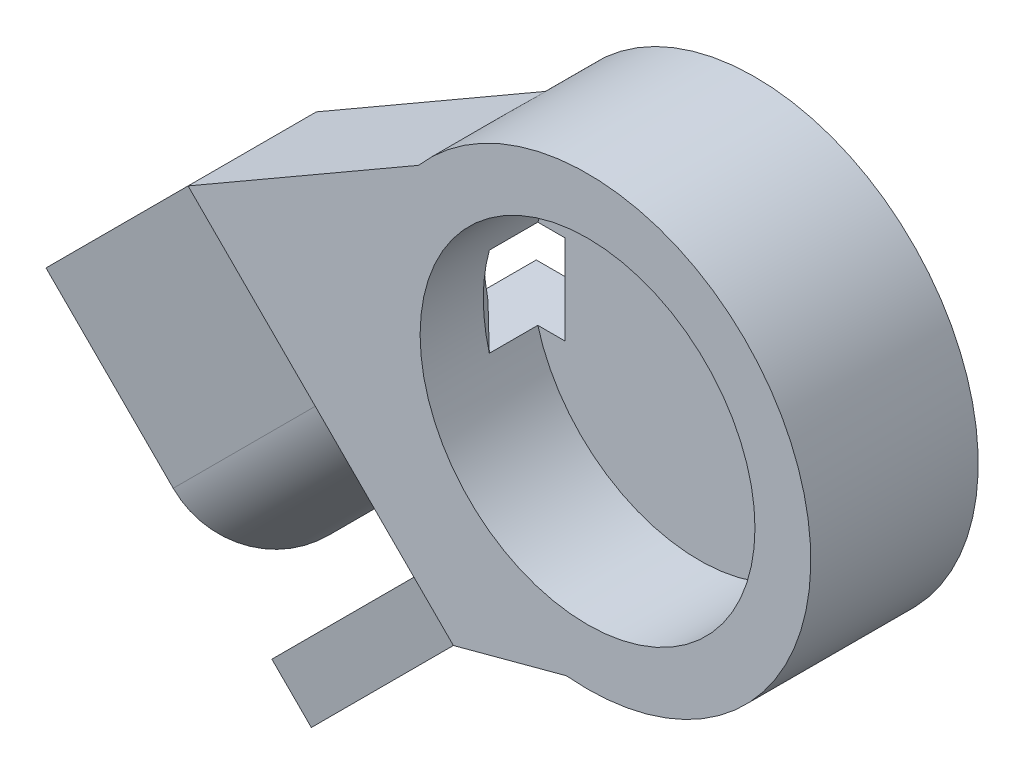
SolidWorks part; units mm, degrees
material "ABS"
ref_plane "Front Plane" through (0, 0, 0) normal (0, 0, 1) x (1, 0, 0)
ref_plane "Top Plane" through (0, 0, 0) normal (0, 1, 0) x (1, 0, 0)
ref_plane "Right Plane" through (0, 0, 0) normal (1, 0, 0) x (0, 0, -1)
ref_plane "Plane1" through (176.1577, 176.1577, 66.7527) normal (0.683, 0.683, 0.2588) x (0.7241, -0.6798, -0.1169)
sketch "Sketch2" plane through (176.1577, 176.1577, 66.7527) normal (0.683, 0.683, 0.2588) x (0.7241, -0.6798, -0.1169)
  line L0 (-5.3415, 21.7837) -> (-15.5015, 23.0219)
  line L1 (-2.3354, 33.3275) -> (-3.5736, 23.1675)
  line L2 (-15.5015, 23.0219) -> (-15.8856, 19.8702)
  line L3 (-2.3354, 33.3275) -> (0.8163, 32.9434)
  line L4 (-1.8445, 37.3551) -> (-3.5736, 23.1675) construction
  line L5 (-5.3415, 21.7837) -> (-19.5291, 23.5127) construction
  line L6 (1.7696, 14.5201) -> (4.8423, 39.7335)
  line L7 (4.8423, 39.7335) -> (4.8373, 39.7342)
  line L8 (1.3071, 36.971) -> (-0.4219, 22.7834)
  line L9 (-5.7256, 18.632) -> (-19.9132, 20.361)
  line L10 (-23.4433, 17.5979) -> (-23.4439, 17.5928)
  line L11 (-23.4439, 17.5928) -> (1.7696, 14.5201)
  line L12 (1.7696, 14.5201) -> (4.8423, 39.7335)
  line L13 (4.8423, 39.7335) -> (4.8373, 39.7342)
  line L14 (1.3071, 36.971) -> (-0.4219, 22.7834)
  line L15 (-5.7256, 18.632) -> (-19.9132, 20.361)
  line L16 (-23.4433, 17.5979) -> (-23.4439, 17.5928)
  line L17 (-23.4439, 17.5928) -> (1.7696, 14.5201)
  line L18 (2.1536, 17.6718) -> (5.3053, 17.2877)
  line L19 (5.3053, 17.2877) -> (7.1197, 32.1752)
  line L20 (7.1197, 32.1752) -> (3.968, 32.5593)
  arc A0 (-5.3415, 21.7837) -> (-3.5736, 23.1675) centre (-5.1494, 23.3595) ccw
  arc A3 (4.8373, 39.7342) -> (1.3071, 36.971) centre (4.4538, 36.5875) ccw
  arc A4 (-5.7256, 18.632) -> (-0.4219, 22.7834) centre (-5.1494, 23.3595) ccw
  arc A5 (-19.9132, 20.361) -> (-23.4433, 17.5979) centre (-20.2966, 17.2144) ccw
  arc A6 (4.8373, 39.7342) -> (1.3071, 36.971) centre (4.4538, 36.5875) ccw
  arc A7 (-5.7256, 18.632) -> (-0.4219, 22.7834) centre (-5.1494, 23.3595) ccw
  arc A8 (-19.9132, 20.361) -> (-23.4433, 17.5979) centre (-20.2966, 17.2144) ccw
  dimension "D3" = 10.16
  dimension "D4" = 3.175
  dimension "D1" = 0
  dimension "D2" = 3.175
extrude "Boss-Extrude1" add sketch "Sketch2" against normal blind 19.05 contours L19 L20 L12 L18 | L15 A7 L14 L3 L1 A0 L0 L2 region at (175.3456, 184.7607, 46.193) region at (181.9107, 179.6657, 42.3135)
ref_plane "Plane2" through (106.9927, 106.9927, 0) normal (0, 0, 1) x (-1, 0, 0)
ref_plane "Plane3" through (0, 0, 49.5568) normal (0, 0, 1) x (1, 0, 0)
sketch "Sketch4" plane through (0, 0, 49.5568) normal (0, 0, 1) x (1, 0, 0)
  line L0 (166.4044, 166.4044) -> (179.4158, 179.4158) construction
  line L1 (166.4044, 166.4044) -> (179.4158, 179.4158)
  line L2 (189.2918, 191.5369) -> (164.4348, 166.6798) construction
  line L3 (166.9041, 171.3942) -> (179.9155, 184.4056) construction
  line L4 (166.9041, 171.3942) -> (179.9155, 184.4056)
  line L5 (178.8118, 178.8118) -> (176.5668, 181.0569)
  line L6 (179.4158, 179.4158) -> (181.6609, 177.1707) construction
  circle A0 centre (189.2918, 191.5369) radius 12.7
  circle A1 centre (189.2918, 191.5369) radius 9.525
  point P9 (177.6893, 179.9344)
  point P10 (180.5383, 178.2933)
  dimension "D2" = 25.4
  dimension "D3" = 19.05
  dimension "D1" = 15.875
extrude "Boss-Extrude2" add sketch "Sketch4" against normal blind 6.35 separate body contours A1 A0 region at (193.2912, 179.8621, 49.5568)
sketch "Sketch5" plane through (0, 0, 49.5568) normal (0, 0, 1) x (1, 0, 0)
  line L0 (181.6609, 177.1707) -> (188.0912, 178.8937)
  line L1 (179.6794, 199.837) -> (166.5658, 192.2658)
  line L3 (166.5658, 192.2658) -> (181.6609, 177.1707)
  line L4 (168.6495, 164.1593) -> (181.6609, 177.1707) construction
  line L5 (153.5544, 179.2544) -> (166.5658, 192.2658) construction
  circle A0 centre (189.2918, 191.5369) radius 12.7 construction
  arc A1 (179.6794, 199.837) -> (188.0912, 178.8937) centre (189.2918, 191.5369) ccw
  dimension "D1" = 30
  dimension "D2" = 15
extrude "Boss-Extrude4" add sketch "Sketch5" along direction (0.183, 0.183, -0.9659) on the side against the normal blind 6.35
sketch "Sketch6" plane through (0, 0, 43.2068) normal (0, 0, -1) x (-1, 0, 0)
  circle A1 centre (-189.2918, 191.5369) radius 12.7
  circle A2 centre (-189.2918, 191.5369) radius 12.7
  dimension "D1" = 0
extrude "Boss-Extrude5" add sketch "Sketch6" along normal blind 3.175
sketch "Sketch7" plane through (0, 0, 40.0318) normal (0, 0, -1) x (-1, 0, 0)
  line L0 (-189.2918, 191.5369) -> (-176.5918, 191.5369)
  line L2 (-181.6718, 188.9969) -> (-176.5918, 188.9969)
  line L3 (-181.6718, 188.9969) -> (-181.6718, 194.0769)
  line L4 (-181.6718, 194.0769) -> (-176.5918, 194.0769)
  line L5 (-176.5918, 188.9969) -> (-176.5918, 194.0769)
  line L6 (-181.6718, 188.9969) -> (-176.5918, 194.0769) construction
  line L7 (-181.6718, 194.0769) -> (-176.5918, 188.9969) construction
  circle A1 centre (-189.2918, 191.5369) radius 12.7
  circle A2 centre (-189.2918, 191.5369) radius 12.7
  point P0 (-179.1318, 191.5369)
  circle M2 centre (-189.2918, 191.5369) radius 12.7
  dimension "D2" = 5.08
  dimension "D3" = 5.08
  dimension "D1" = 0
extrude "Cut-Extrude1" cut sketch "Sketch7" against normal up to surface (3.3914 mm away) contours L4 L3 L0 M2 | L3 L2 L0 M2 region at (179.1738, 192.796, 40.0318) region at (179.1738, 190.2777, 40.0318) up to face at (177.5992, 185.6411, 43.4232)
chamfer "Chamfer1" distance 2.54 angle 45 1 edges at (179.7668, 191.5369, 43.4232)
